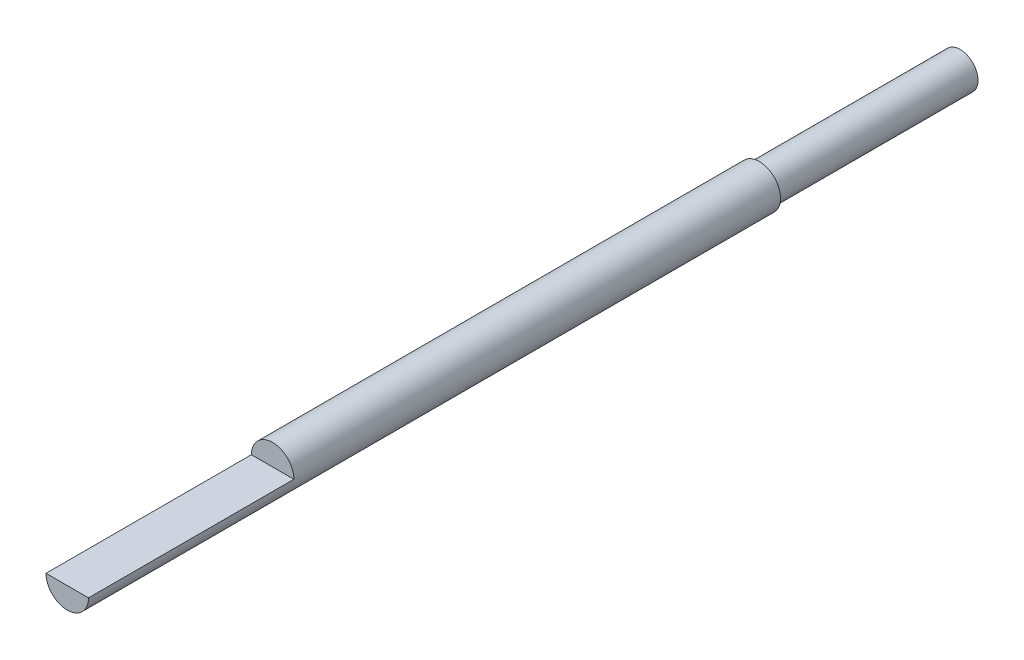
SolidWorks part; units mm, degrees
ref_plane "Front Plane" through (0, 0, 0) normal (0, 0, 1) x (1, 0, 0)
ref_plane "Top Plane" through (0, 0, 0) normal (0, 1, 0) x (1, 0, 0)
ref_plane "Right Plane" through (0, 0, 0) normal (1, 0, 0) x (0, 0, -1)
sketch "Sketch1" plane through (0, 0, 0) normal (0, 0, 1) x (1, 0, 0)
  circle A0 centre (0, 0) radius 4.7625
  dimension "D1" = 9.525
extrude "Boss-Extrude1" add sketch "Sketch1" along normal blind 200
sketch "Sketch2" plane through (0, 0, 200) normal (0, 0, 1) x (1, 0, 0)
  line L1 (-4.7625, 0) -> (4.7625, 0)
  circle A0 centre (0, 0) radius 4.7625
  circle M2 centre (0, 0) radius 4.7625
  dimension "D2" = 9.525
extrude "Cut-Extrude1" cut sketch "Sketch2" against normal blind 46 contours M2 region at (0, 2.0213, 200)
sketch "Sketch3" plane through (0, 0, 0) normal (0, 0, -1) x (-1, 0, 0)
  circle A0 centre (0, 0) radius 4.7625
  circle A1 centre (0, 0) radius 4
  dimension "D1" = 9.525
  dimension "D2" = 8
extrude "Cut-Extrude2" cut sketch "Sketch3" against normal blind 45
